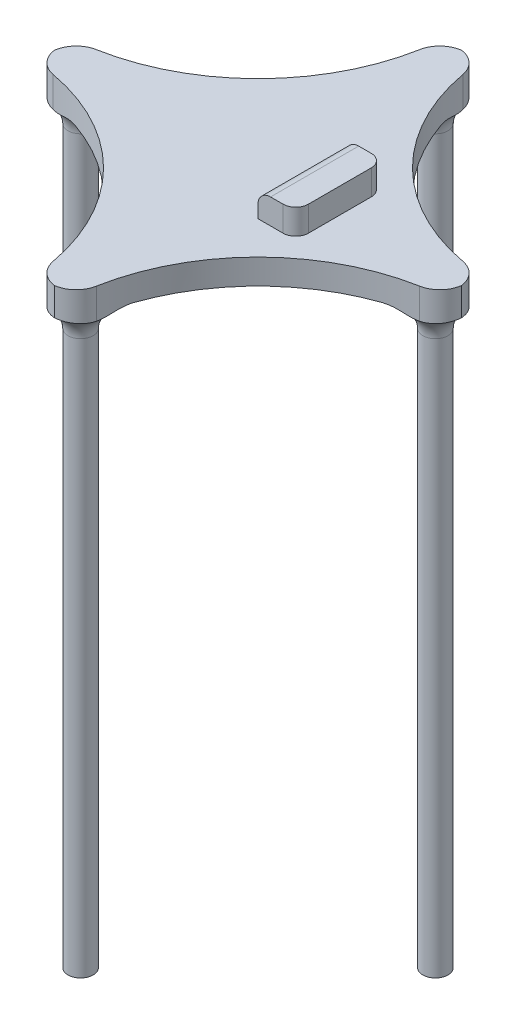
SolidWorks part; units mm, degrees
ref_plane "Alzado" through (0, 0, 0) normal (0, 0, 1) x (1, 0, 0)
ref_plane "Planta" through (0, 0, 0) normal (0, 1, 0) x (1, 0, 0)
ref_plane "Vista lateral" through (0, 0, 0) normal (1, 0, 0) x (0, 0, -1)
sketch "Croquis1" plane through (0, 0, 0) normal (0, 1, 0) x (1, 0, 0)
  line L1 (-7.5, 81) -> (7.5, 81)
  line L2 (-7.5, 81) -> (-7.5, -81)
  line L3 (-7.5, -81) -> (7.5, -81)
  line L4 (7.5, 81) -> (7.5, -81)
  line L5 (-7.5, 81) -> (7.5, -81) construction
  line L6 (-7.5, -81) -> (7.5, 81) construction
  line L7 (-81, 7.5) -> (81, 7.5)
  line L8 (-81, 7.5) -> (-81, -7.5)
  line L9 (-81, -7.5) -> (81, -7.5)
  line L10 (81, 7.5) -> (81, -7.5)
  line L11 (-81, 7.5) -> (81, -7.5) construction
  line L12 (-81, -7.5) -> (81, 7.5) construction
  point P0 (0, 0)
  point P6 (0, 0)
  dimension "D1" = 15
  dimension "D2" = 15
  dimension "D3" = 162
  dimension "D4" = 162
extrude "Saliente-Extruir1" add sketch "Croquis1" along normal blind 10 contours L2 L9 L4 L7 | L2 L7 L4 L1 | L10 L7 L4 L9 | L8 L9 L2 L7 | L9 L2 L3 L4 region at (0, 0, -44.25) region at (0, 0, 0) region at (-44.25, 0, 0) region at (44.25, 0, 0) region at (0, 0, 44.25)
sketch "Croquis3" plane through (0, 0, 0) normal (0, -1, 0) x (-1, 0, 0)
  circle A0 centre (0, 0) radius 2.5
  circle A1 centre (0, 0) radius 6
  dimension "D1" = 5
  dimension "D2" = 12
  dimension "D3" = 7.5
  dimension "D4" = 7.5
  dimension "D5" = 7.5
  dimension "D6" = 7.5
extrude "Saliente-Extruir3" add sketch "Croquis3" along normal blind 10
fillet "Redondeo4" radius 3 1 edges at (0, 0, 6)
sketch "Croquis4" plane through (0, 0, 0) normal (0, 0, -1) x (-1, 0, 0)
  line L1 (7.5, 0) -> (-7.5, 0) construction
  circle A1 centre (0, -5.5) radius 0.75
  dimension "D2" = 1.5
  dimension "D3" = 5.5
extrude "Cortar-Extruir1" cut sketch "Croquis4" against normal up to surface and the other way up to surface up to face at (0, -3, 6) other way up to face at (0, -3, 6)
sketch "Croquis2" plane through (0, 0, 0) normal (0, -1, 0) x (-1, 0, 0)
  line L0 (7.5, -81) -> (-7.5, -81) construction
  line L1 (-7.5, -7.5) -> (-7.5, -81) construction
  line L2 (81, 7.5) -> (81, -7.5) construction
  line L3 (7.5, 81) -> (-7.5, 81) construction
  line L4 (-81, 7.5) -> (-81, -7.5) construction
  line L5 (-7.5, 81) -> (-7.5, 7.5) construction
  line L6 (-7.5, -7.5) -> (-81, -7.5) construction
  line L7 (81, 7.5) -> (7.5, 7.5) construction
  circle A0 centre (0, 70.5) radius 5
  circle A1 centre (-70.5, 0) radius 5
  circle A2 centre (70.5, 0) radius 5
  circle A3 centre (0, -70.5) radius 5
  dimension "D1" = 10
  dimension "D2" = 10
  dimension "D3" = 10
  dimension "D4" = 10
  dimension "D5" = 10.5
  dimension "D6" = 7.5
  dimension "D7" = 10.5
  dimension "D8" = 10.5
  dimension "D9" = 10.5
  dimension "D10" = 7.5
  dimension "D11" = 7.5
  dimension "D12" = 7.5
extrude "Saliente-Extruir2" add sketch "Croquis2" along normal blind 230
fillet "Redondeo1" radius 80 4 edges at (7.5, 5, 7.5) (-7.5, 5, -7.5) (-7.5, 5, 7.5) (7.5, 5, -7.5)
fillet "Redondeo3" radius 10 8 edges at (7.5, 5, 81) (-7.5, 5, 81) (81, 5, 7.5) (81, 5, -7.5) (7.5, 5, -81) (-7.5, 5, -81) (-81, 5, -7.5) (-81, 5, 7.5)
fillet "Redondeo5" radius 10 4 edges at (0, 0, 75.5) (70.5, 0, 5) (-70.5, 0, 5) (0, 0, -65.5)
sketch "Croquis8" plane through (0, 10, 0) normal (0, 1, 0) x (1, 0, 0)
  line L1 (17.5, 17.5) -> (32.5, 17.5)
  line L2 (17.5, 17.5) -> (17.5, -17.5)
  line L3 (17.5, -17.5) -> (32.5, -17.5)
  line L4 (32.5, 17.5) -> (32.5, -17.5)
  line L5 (17.5, 17.5) -> (32.5, -17.5) construction
  line L6 (17.5, -17.5) -> (32.5, 17.5) construction
  point P0 (25, 0)
  dimension "D1" = 25
  dimension "D2" = 35
  dimension "D3" = 15
extrude "Saliente-Extruir5" add sketch "Croquis8" along normal blind 10
sketch "Croquis5" plane through (0, 0, 0) normal (0, -1, 0) x (1, 0, 0)
  line L1 (21.5, 10) -> (28.5, 10)
  line L2 (21.5, 10) -> (21.5, -10)
  line L3 (21.5, -10) -> (28.5, -10)
  line L4 (28.5, 10) -> (28.5, -10)
  line L5 (21.5, 10) -> (28.5, -10) construction
  line L6 (21.5, -10) -> (28.5, 10) construction
  point P0 (25, 0)
  dimension "D1" = 25
  dimension "D2" = 7
  dimension "D3" = 20
extrude "Cortar-Extruir3" cut sketch "Croquis5" against normal blind 15
sketch "Croquis9" plane through (17.5, 0, 0) normal (-1, 0, 0) x (0, 0, 1)
  line L0 (-17.5, 10) -> (17.5, 10) construction
  line L1 (-10, 15) -> (10, 15)
  line L2 (-10, 15) -> (-10, 10)
  line L3 (-10, 10) -> (10, 10)
  line L4 (10, 15) -> (10, 10)
  line L5 (-10, 15) -> (10, 10) construction
  line L6 (-10, 10) -> (10, 15) construction
  line L7 (0, -1.1106) -> (0, 10) construction
  point P0 (0, 12.5)
  point P7 (0, 0)
  point P10 (0, 4.4447)
  point P11 (0, 10)
  dimension "D1" = 5
  dimension "D2" = 20
extrude "Cortar-Extruir4" cut sketch "Croquis9" against normal up to next
fillet "Redondeo6" radius 2 1 edges at (21.5, 10, 0)
fillet "Redondeo7" radius 2 3 edges at (17.5, 12.5, 10) (17.5, 15, 0) (17.5, 12.5, -10)
fillet "Redondeo8" radius 5 1 edges at (17.5, 20, 0)
fillet "Redondeo9" radius 5 2 edges at (32.5, 15, -17.5) (32.5, 15, 17.5)
